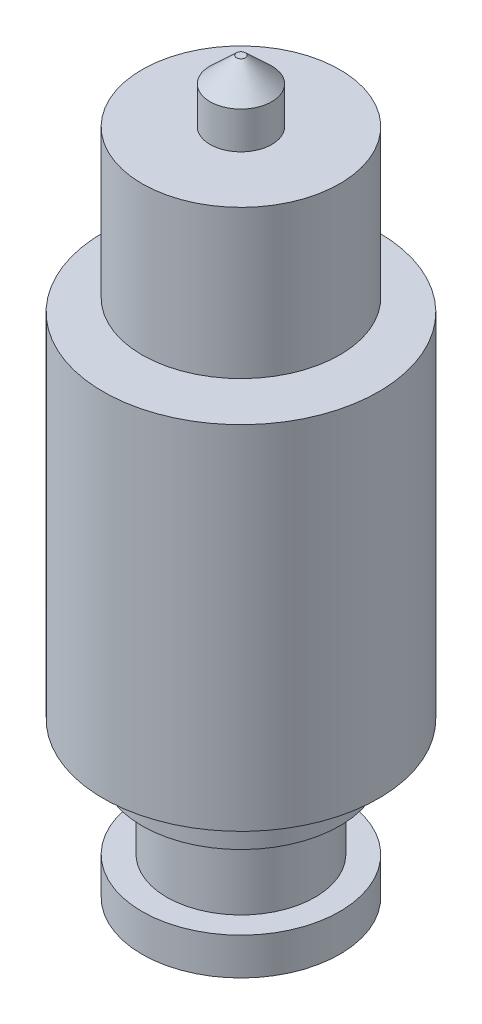
SolidWorks part; units mm, degrees
material "AISI 1035 Steel (SS)"
ref_plane "Front Plane" through (0, 0, 0) normal (0, 0, 1) x (1, 0, 0)
ref_plane "Top Plane" through (0, 0, 0) normal (0, 1, 0) x (1, 0, 0)
ref_plane "Right Plane" through (0, 0, 0) normal (1, 0, 0) x (0, 0, -1)
sketch "Sketch1" plane through (0, 0, 0) normal (0, 1, 0) x (1, 0, 0)
  circle A0 centre (0, 0) radius 8
  dimension "D1" = 16
extrude "Boss-Extrude1" add sketch "Sketch1" along normal blind 3
sketch "Sketch2" plane through (0, 3, 0) normal (0, 1, 0) x (1, 0, 0)
  circle A0 centre (0, 0) radius 6
  dimension "D1" = 12
extrude "Boss-Extrude2" add sketch "Sketch2" along normal blind 6
sketch "Sketch3" plane through (0, 9, 0) normal (0, 1, 0) x (1, 0, 0)
  circle A0 centre (0, 0) radius 8
  dimension "D1" = 16
extrude "Boss-Extrude3" add sketch "Sketch3" along normal blind 1.5
sketch "Sketch4" plane through (0, 10.5, 0) normal (0, 1, 0) x (1, 0, 0)
  circle A0 centre (0, 0) radius 5
  dimension "D1" = 10
extrude "Boss-Extrude4" add sketch "Sketch4" along normal blind 2
sketch "Sketch5" plane through (0, 12.5, 0) normal (0, 1, 0) x (1, 0, 0)
  circle A0 centre (0, 0) radius 11.15
  dimension "D1" = 22.3
extrude "Boss-Extrude5" add sketch "Sketch5" along normal blind 28.5
sketch "Sketch6" plane through (0, 41, 0) normal (0, 1, 0) x (1, 0, 0)
  circle A0 centre (0, 0) radius 2
  dimension "D1" = 4
extrude "Boss-Extrude6" add sketch "Sketch6" along normal blind 1
sketch "Sketch7" plane through (0, 42, 0) normal (0, 1, 0) x (1, 0, 0)
  circle A0 centre (0, 0) radius 8
  dimension "D1" = 16
extrude "Boss-Extrude7" add sketch "Sketch7" along normal blind 12
sketch "Sketch8" plane through (0, 54, 0) normal (0, 1, 0) x (1, 0, 0)
  circle A0 centre (0, 0) radius 2.5
  dimension "D1" = 5
extrude "Boss-Extrude8" add sketch "Sketch8" along normal blind 3
sketch "Sketch9" plane through (0, 57, 0) normal (0, 1, 0) x (1, 0, 0)
  circle A0 centre (0, 0) radius 2.5
extrude "Boss-Extrude9" add sketch "Sketch9" along normal blind 2 draft 47
ref_plane "Plane1" through (0, 0, 0) normal (0, 0, 1) x (1, 0, 0)
sketch "草图1" plane through (0, 0, 0) normal (0, -1, 0) x (-1, 0, 0)
  circle A0 centre (0, 0) radius 2.5
  dimension "D1" = 5
extrude "切除-拉伸1" cut sketch "草图1" against normal blind 10
equation "\"D1@Boss-Extrude5\"=43-12.5-2"
